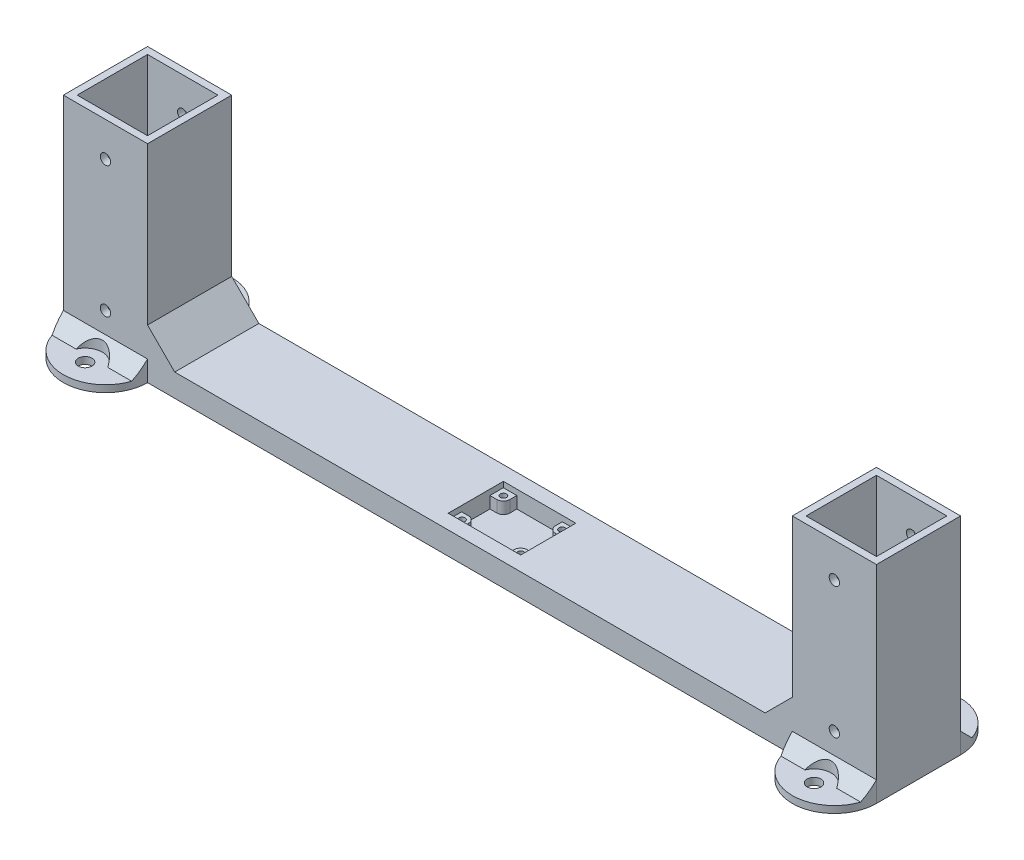
SolidWorks part; units mm, degrees
ref_plane "Front Plane" through (0, 0, 0) normal (0, 0, 1) x (1, 0, 0)
ref_plane "Top Plane" through (0, 0, 0) normal (0, 1, 0) x (1, 0, 0)
ref_plane "Right Plane" through (0, 0, 0) normal (1, 0, 0) x (0, 0, -1)
sketch "Sketch1" plane through (0, 0, 0) normal (0, 1, 0) x (1, 0, 0)
  line L0 (0, 66.2925) -> (0, -63.9072) construction
  line L1 (149.6822, -15.494) -> (118.6942, -15.494)
  line L2 (-121.2342, 12.954) -> (-147.1422, 12.954)
  line L3 (-121.2342, 12.954) -> (-121.2342, -12.954)
  line L4 (-121.2342, -12.954) -> (-147.1422, -12.954)
  line L5 (-147.1422, 12.954) -> (-147.1422, -12.954)
  line L6 (-149.6822, 15.494) -> (-118.6942, 15.494)
  line L7 (-149.6822, 15.494) -> (-149.6822, -15.494)
  line L8 (-149.6822, -15.494) -> (-118.6942, -15.494)
  line L9 (-118.6942, 15.494) -> (-118.6942, -15.494)
  line L10 (121.2342, -12.954) -> (147.1422, -12.954)
  line L11 (121.2342, 12.954) -> (121.2342, -12.954)
  line L12 (118.6942, 15.494) -> (118.6942, -15.494)
  line L13 (149.6822, 15.494) -> (118.6942, 15.494)
  line L14 (149.6822, 15.494) -> (149.6822, -15.494)
  line L15 (147.1422, 12.954) -> (147.1422, -12.954)
  line L16 (121.2342, 12.954) -> (147.1422, 12.954)
  point P12 (-118.6942, 0)
  dimension "D1" = 25.908
  dimension "D2" = 2.54
  dimension "D3" = 2.54
  dimension "D4" = 2.54
  dimension "D5" = 121.2342
extrude "Boss-Extrude1" add sketch "Sketch1" along normal blind 76.2
sketch "Sketch2" plane through (0, 0, 0) normal (0, 1, 0) x (1, 0, 0)
  line L1 (-118.6942, 15.494) -> (118.6942, 15.494)
  line L2 (-118.6942, 15.494) -> (-118.6942, -15.494)
  line L3 (-118.6942, -15.494) -> (118.6942, -15.494)
  line L4 (118.6942, 15.494) -> (118.6942, -15.494)
extrude "Boss-Extrude2" add sketch "Sketch2" along normal blind 8.382
chamfer "Chamfer1" distance 10 angle 45 2 edges at (118.6942, 8.382, 0) (-118.6942, 8.382, 0)
sketch "Sketch3" plane through (0, 0, 0) normal (0, 1, 0) x (1, 0, 0)
  line L0 (0, 73.3763) -> (0, -49.9168) construction
  line L1 (-149.6822, 15.494) -> (-118.6942, 15.494)
  line L2 (-149.6822, 15.494) -> (-149.6822, -15.494)
  line L3 (-149.6822, -15.494) -> (-118.6942, -15.494)
  line L4 (-118.6942, 15.494) -> (-118.6942, -15.494)
  line L5 (-105.2543, 0) -> (132.938, 0) construction
  line L6 (149.6822, 15.494) -> (118.6942, 15.494)
  line L7 (149.6822, -15.494) -> (118.6942, -15.494)
  line L8 (-149.6822, -15.494) -> (-118.6942, -15.494)
  arc A0 (-149.6822, 15.494) -> (-118.6942, 15.494) centre (-134.1882, 15.494) cw
  circle A1 centre (-134.1882, 22.988) radius 2.54
  circle A2 centre (134.1882, 22.988) radius 2.54
  arc A3 (149.6822, 15.494) -> (118.6942, 15.494) centre (134.1882, 15.494) ccw
  circle A4 centre (134.1882, -22.988) radius 2.54
  arc A5 (149.6822, -15.494) -> (118.6942, -15.494) centre (134.1882, -15.494) cw
  circle A6 centre (-134.1882, -22.988) radius 2.54
  arc A7 (-149.6822, -15.494) -> (-118.6942, -15.494) centre (-134.1882, -15.494) ccw
  point P9 (-134.1882, 30.988)
  dimension "D1" = 5.08
  dimension "D3" = 7.494
  dimension "D2" = 8
extrude "Boss-Extrude4" add sketch "Sketch3" along normal blind 2.54 contours L3 A7 A6 | A0 L1 A1 | L6 A3 A2 | A5 L7 A4 region at (-134.1882, 0, -30.6415) region at (-134.1882, 0, 15.8405) region at (134.1882, 0, -15.8405) region at (134.1882, 0, 30.6415)
chamfer "Chamfer4" distance 5 angle 45 4 edges at (134.1882, 2.54, -15.494) (134.1882, 2.54, 15.494) (-134.1882, 2.54, 15.494) (-134.1882, 2.54, -15.494)
sketch "Sketch5" plane through (0, 2.54, 0) normal (0, 1, 0) x (1, 0, 0)
  line L0 (0, 86.151) -> (0, -107.1541) construction
  line L1 (-119.1711, 0) -> (177.2282, 0) construction
  circle A0 centre (-134.1882, 22.988) radius 6.35
  circle A1 centre (134.1882, 22.988) radius 6.35
  circle A2 centre (134.1882, -22.988) radius 6.35
  circle A3 centre (-134.1882, -22.988) radius 6.35
  dimension "D1" = 12.7
extrude "Cut-Extrude2" cut sketch "Sketch5" along normal through all
sketch "Sketch7" plane through (0, 0, 0) normal (0, 1, 0) x (1, 0, 0)
  line L1 (-147.1422, 12.954) -> (-121.2342, 12.954)
  line L2 (-147.1422, 12.954) -> (-147.1422, -12.954)
  line L3 (-147.1422, -12.954) -> (-121.2342, -12.954)
  line L4 (-121.2342, 12.954) -> (-121.2342, -12.954)
  line L5 (147.1422, 12.954) -> (121.2342, 12.954)
  line L6 (147.1422, 12.954) -> (147.1422, -12.954)
  line L7 (147.1422, -12.954) -> (121.2342, -12.954)
  line L8 (121.2342, 12.954) -> (121.2342, -12.954)
extrude "Boss-Extrude5" add sketch "Sketch7" along normal blind 2.54
sketch "Sketch8" plane through (0, 0, 15.494) normal (0, 0, 1) x (1, 0, 0)
  line L0 (-134.1882, 76.2) -> (-134.1882, 0) construction
  line L1 (-149.6822, 76.2) -> (-118.6942, 76.2) construction
  line L2 (-149.6822, 0) -> (-118.6942, 0) construction
  line L3 (0, 28.5413) -> (0, -23.9354) construction
  circle A0 centre (-134.1882, 15.24) radius 1.905
  circle A1 centre (134.1882, 15.24) radius 1.905
  circle A2 centre (-134.1882, 63.5) radius 1.905
  circle A3 centre (134.1882, 63.5) radius 1.905
  dimension "D1" = 15.24
  dimension "D2" = 3.81
  dimension "D3" = 12.7
extrude "Cut-Extrude3" cut sketch "Sketch8" against normal through all both and the other way through all
sketch "Sketch12" plane through (0, 8.382, 0) normal (0, 1, 0) x (1, 0, 0)
  line L1 (13.335, -10.16) -> (-13.335, -10.16)
  line L2 (13.335, -10.16) -> (13.335, 10.16)
  line L3 (13.335, 10.16) -> (-13.335, 10.16)
  line L4 (-13.335, -10.16) -> (-13.335, 10.16)
  point P4 (-13.335, 0)
  point P6 (0, -10.16)
  dimension "D1" = 20.32
  dimension "D2" = 26.67
extrude "Cut-Extrude4" cut sketch "Sketch12" against normal blind 6.35
sketch "Sketch14" plane through (0, 2.032, 0) normal (0, 1, 0) x (1, 0, 0)
  line L0 (-13.335, 10.16) -> (-13.335, -10.16) construction
  line L1 (-13.335, -10.16) -> (13.335, -10.16) construction
  line L2 (-13.335, 0) -> (13.335, 0) construction
  line L3 (-13.335, 10.16) -> (-13.335, -10.16) construction
  line L4 (13.335, -10.16) -> (13.335, 10.16) construction
  line L5 (0, -10.16) -> (0, 10.16) construction
  line L6 (-13.335, -10.16) -> (13.335, -10.16) construction
  line L7 (13.335, 10.16) -> (-13.335, 10.16) construction
  line L8 (-8.382, -7.62) -> (-8.382, -10.16)
  line L9 (-10.795, -5.207) -> (-13.335, -5.207)
  line L10 (-13.335, -5.207) -> (-13.335, -10.16)
  line L11 (-13.335, -10.16) -> (-8.382, -10.16)
  line L12 (8.382, -7.62) -> (8.382, -10.16)
  line L13 (13.335, -10.16) -> (8.382, -10.16)
  line L14 (13.335, -5.207) -> (13.335, -10.16)
  line L15 (10.795, -5.207) -> (13.335, -5.207)
  line L16 (8.382, 7.62) -> (8.382, 10.16)
  line L17 (10.795, 5.207) -> (13.335, 5.207)
  line L18 (13.335, 5.207) -> (13.335, 10.16)
  line L19 (13.335, 10.16) -> (8.382, 10.16)
  line L20 (-8.382, 7.62) -> (-8.382, 10.16)
  line L21 (-13.335, 10.16) -> (-8.382, 10.16)
  line L22 (-13.335, 5.207) -> (-13.335, 10.16)
  line L23 (-10.795, 5.207) -> (-13.335, 5.207)
  circle A0 centre (-10.795, -7.62) radius 1.143
  arc A1 (-8.382, -7.62) -> (-10.795, -5.207) centre (-10.795, -7.62) ccw
  arc A2 (8.382, 7.62) -> (10.795, 5.207) centre (10.795, 7.62) ccw
  circle A3 centre (-10.795, 7.62) radius 1.143
  circle A4 centre (10.795, 7.62) radius 1.143
  arc A5 (8.382, -7.62) -> (10.795, -5.207) centre (10.795, -7.62) cw
  arc A6 (-8.382, 7.62) -> (-10.795, 5.207) centre (-10.795, 7.62) cw
  circle A7 centre (10.795, -7.62) radius 1.143
  dimension "D3" = 2.286
  dimension "D4" = 1.27
  dimension "D1" = 2.54
  dimension "D2" = 2.54
extrude "Boss-Extrude7" add sketch "Sketch14" along normal blind 4.318
